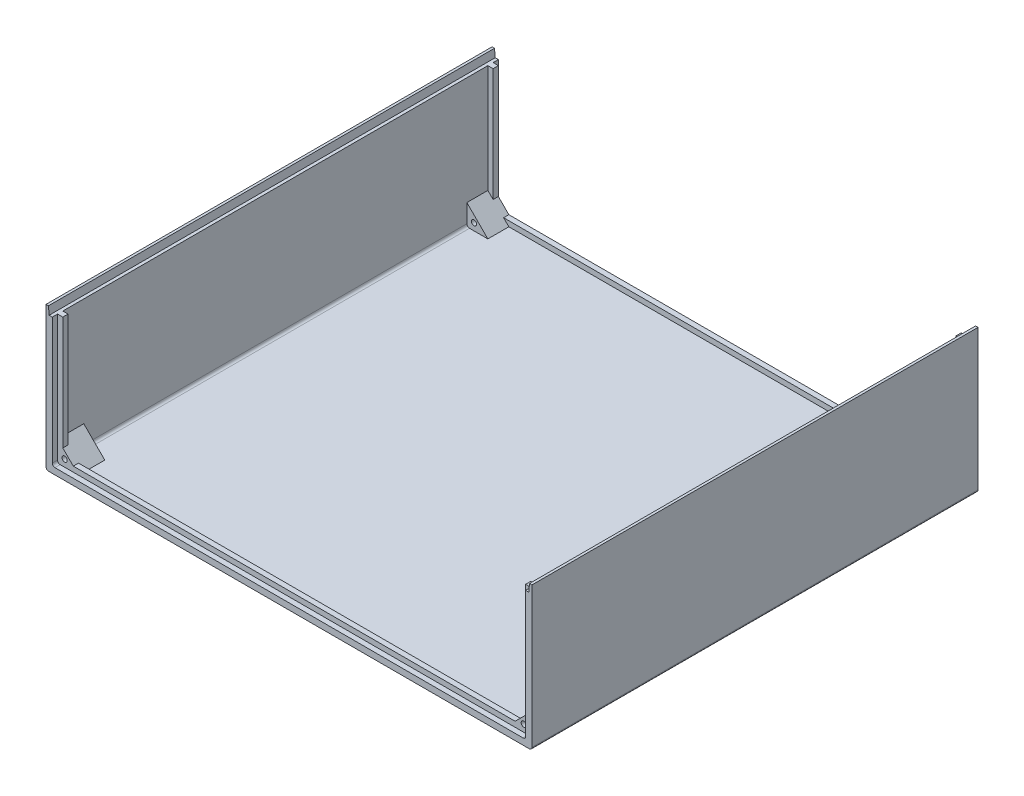
SolidWorks part; units mm, degrees
ref_plane "Спереди" through (0, 0, 0) normal (0, 0, 1) x (1, 0, 0)
ref_plane "Сверху" through (0, 0, 0) normal (0, 1, 0) x (1, 0, 0)
ref_plane "Справа" through (0, 0, 0) normal (1, 0, 0) x (0, 0, -1)
sketch "Эскиз1" plane through (0, 0, 0) normal (0, 0, 1) x (1, 0, 0)
  line L0 (0, 49.2) -> (0, 0)
  line L1 (0, 0) -> (180.4, 0) construction
  line L2 (0, 0) -> (0, 98.4) construction
  line L3 (0, 98.4) -> (180.4, 98.4) construction
  line L4 (180.4, 0) -> (180.4, 98.4) construction
  line L5 (0, 0) -> (180.4, 0)
  line L6 (180.4, 0) -> (180.4, 49.2)
  line L11 (182.8, -2.4) -> (-2.4, -2.4)
  line L16 (0, 8) -> (8, 0)
  line L17 (180.4, 8) -> (172.4, 0)
  line L18 (2.7, 98.4) -> (2.7, 0) construction
  line L19 (177.7, 98.4) -> (177.7, 0) construction
  line L20 (0, 2.7) -> (180.4, 2.7) construction
  line L21 (180.4, 49.2) -> (182.8, 49.2)
  line L22 (182.8, 49.2) -> (182.8, -2.4)
  line L23 (0, 49.2) -> (-2.4, 49.2)
  line L24 (-2.4, 49.2) -> (-2.4, -2.4)
  line L25 (0, 49.2) -> (2, 49.2)
  line L26 (2, 49.2) -> (2, 6)
  line L27 (6, 2) -> (174.4, 2)
  line L28 (180.4, 49.2) -> (178.4, 49.2)
  line L29 (178.4, 49.2) -> (178.4, 6)
  circle A0 centre (177.7, 2.7) radius 1
  circle A1 centre (2.7, 2.7) radius 1
  dimension "D5" = 2
  dimension "D6" = 2
  dimension "D1" = 180.4
  dimension "D2" = 98.4
  dimension "D3" = 2.4
  dimension "D4" = 2.4
  dimension "D7" = 2
  dimension "D8" = 2
  dimension "D9" = 2.4
  dimension "D10" = 2.7
  dimension "D11" = 2.7
  dimension "D12" = 2.7
  dimension "D13" = 8
  dimension "D14" = 8
  dimension "D15" = 8
  dimension "D16" = 8
  dimension "D17" = 2
extrude "Бобышка-Вытянуть1" add sketch "Эскиз1" along normal blind 170 contours L23 L24 L11 L22 L21 L6 L5 L0 region at (-1.9225, 28.6, 0)
extrude "Бобышка-Вытянуть2" add sketch "Эскиз1<3>" along normal blind 10 from offset 2 contours L16 L0 L5 A1 | L6 L17 L5 A0 region at (0.92, 6.92, 0) region at (173.48, 0.92, 0)
sketch "Эскиз1<3>" plane through (0, 0, 0) normal (0, 0, 1) x (1, 0, 0) same geometry as "Эскиз1"
extrude "Бобышка-Вытянуть3" add sketch "Эскиз1<4>" along normal blind 2 from offset 2 contours L28 L29 L17 L6 | L27 L16 L5 L17 | L26 L25 L0 L16 region at (1.0079, 28.0961, 0) region at (90.2, 1.004, 0) region at (179.3921, 28.0961, 0)
sketch "Эскиз1<4>" plane through (0, 0, 0) normal (0, 0, 1) x (1, 0, 0) same geometry as "Эскиз1"
fillet "Скругление1" radius 1 4 edges at (-2.4, -2.4, 85) (182.8, -2.4, 85) (180.4, 0, 1) (0, 0, 1)
extrude "Бобышка-Вытянуть4" add sketch "Эскиз1<5>" along normal blind 10 from offset 158 contours L6 L17 L5 A0 | L16 L0 L5 A1 region at (0.92, 6.92, 0) region at (173.48, 0.92, 0)
sketch "Эскиз1<5>" plane through (0, 0, 0) normal (0, 0, 1) x (1, 0, 0) same geometry as "Эскиз1"
extrude "Бобышка-Вытянуть5" add sketch "Эскиз1<6>" along normal blind 2 from offset 166 contours L28 L29 L17 L6 | L27 L16 L5 L17 | L26 L25 L0 L16 region at (1.0079, 28.0961, 0) region at (90.2, 1.004, 0) region at (179.3921, 28.0961, 0)
sketch "Эскиз1<6>" plane through (0, 0, 0) normal (0, 0, 1) x (1, 0, 0) same geometry as "Эскиз1"
fillet "Скругление2" radius 1 2 edges at (0, 0, 85) (180.4, 0, 85)
sketch "Эскиз2" plane through (0, 49.2, 0) normal (0, 1, 0) x (1, 0, 0)
  line L0 (0, -170) -> (-2.4, -170) construction
  line L1 (-2.4, 0) -> (-1.2, 0)
  line L2 (-2.4, 0) -> (-2.4, -170)
  line L3 (-2.4, -170) -> (-1.2, -170)
  line L4 (-1.2, 0) -> (-1.2, -170)
  line L5 (180.4, -170) -> (182.8, -170) construction
  line L6 (182.8, 0) -> (181.6, 0)
  line L7 (182.8, 0) -> (182.8, -170)
  line L8 (182.8, -170) -> (181.6, -170)
  line L9 (181.6, 0) -> (181.6, -170)
  dimension "D1" = 1.2
  dimension "D2" = 1.2
extrude "Бобышка-Вытянуть6" add sketch "Эскиз2" along normal blind 3
chamfer "Фаска1" distance 3 angle 5 1 edges at (-1.2, 52.2, 85) first distance on face at (-1.2, 50.7, 85)
chamfer "Фаска2" distance 3 angle 5 1 edges at (181.6, 52.2, 85) first distance on face at (181.6, 50.7, 85)
fillet "Скругление3" radius 1 2 edges at (180.4, 0, 169) (0, 0, 169)
